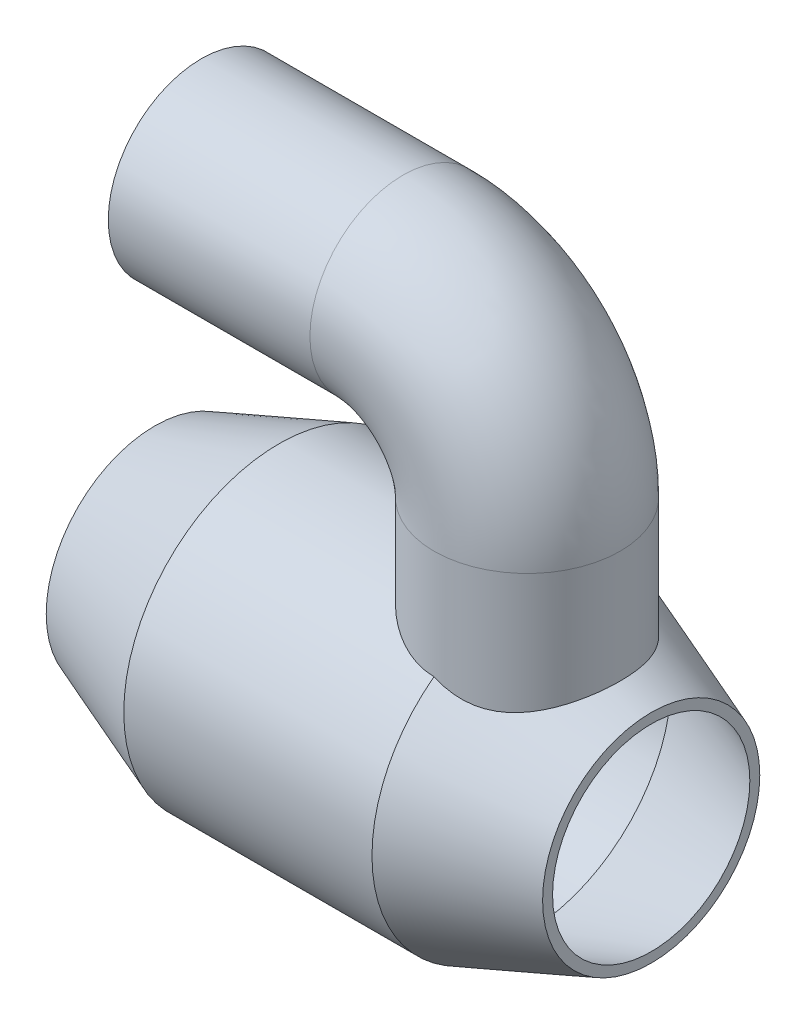
SolidWorks part; units mm, degrees
ref_plane "前基準面" through (0, 0, 0) normal (0, 0, 1) x (1, 0, 0)
ref_plane "上基準面" through (0, 0, 0) normal (0, 1, 0) x (1, 0, 0)
ref_plane "右基準面" through (0, 0, 0) normal (1, 0, 0) x (0, 0, -1)
sketch "草圖2" plane through (0, 0, 0) normal (0, 0, 1) x (1, 0, 0)
  line L0 (-81.5238, 0) -> (85.3333, 0) construction
  line L1 (-80, 35) -> (-40, 50)
  line L2 (-40, 50) -> (40, 50)
  line L3 (0, 29.3333) -> (0, -20.9524) construction
  line L4 (80, 35) -> (40, 50)
  line L5 (-80, 35) -> (-80, 0)
  line L6 (-80, 0) -> (80, 0)
  line L7 (80, 0) -> (80, 35)
  line L8 (40, 50) -> (40, 0) construction
  point P10 (0, 50)
  dimension "D1" = 80
  dimension "D2" = 70
  dimension "D3" = 100
  dimension "D4" = 160
revolve "旋轉3" add sketch "草圖2" angle 360 about L0
sketch "草圖4" plane through (0, 0, 0) normal (0, 1, 0) x (1, 0, 0)
  line L0 (-80, 0) -> (80, 0) construction
  circle A0 centre (40, 0) radius 30
  point P4 (0, 0)
  dimension "D1" = 60
sketch "草圖3" plane through (0, 0, 0) normal (0, 0, 1) x (1, 0, 0)
  line L0 (-65, 115) -> (0, 115)
  line L1 (40, 75) -> (40, 0)
  line L2 (70, 0) -> (10, 0) construction
  arc A0 (40, 75) -> (0, 115) centre (0, 75) ccw
  dimension "D1" = 40
  dimension "D2" = 75
  dimension "D3" = 65
sweep "掃出1" add profiles "草圖4" path "草圖3"
shell "薄殼1" thickness 3 removed face at (80, 0, 35) removed face at (-80, 0, 35) removed face at (-65, 115, 30)
